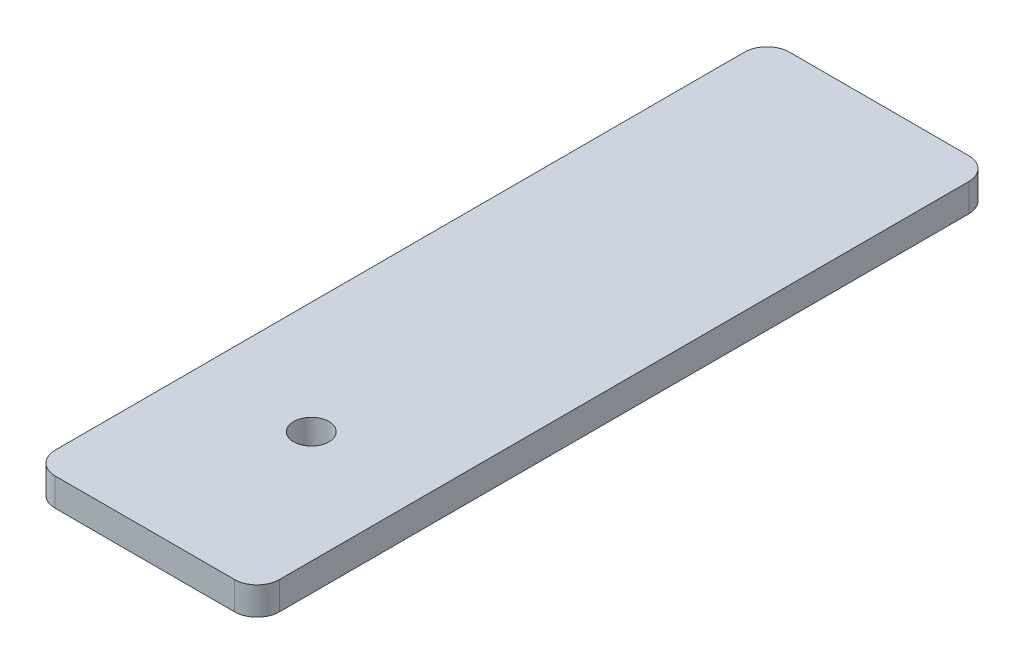
SolidWorks part; units mm, degrees
material "Acrylic (Medium-high impact)"
ref_plane "Front Plane" through (0, 0, 0) normal (0, 0, 1) x (1, 0, 0)
ref_plane "Top Plane" through (0, 0, 0) normal (0, 1, 0) x (1, 0, 0)
ref_plane "Right Plane" through (0, 0, 0) normal (1, 0, 0) x (0, 0, -1)
ref_plane "Plane1" through (0, 0, 0) normal (0, 1, 0) x (1, 0, 0)
sketch "Sketch1" plane through (0, 0, 0) normal (0, 1, 0) x (1, 0, 0)
  line L1 (-26.2811, -26.9588) -> (-0.8811, -26.9588)
  line L2 (-26.2811, -26.9588) -> (-26.2811, 56.2162)
  line L3 (-26.2811, 56.2162) -> (-0.8811, 56.2162)
  line L4 (-0.8811, -26.9588) -> (-0.8811, 56.2162)
  dimension "D1" = 83.175
  dimension "D2" = 25.4
extrude "Boss-Extrude1" add sketch "Sketch1" along normal blind 3.175
sketch "Sketch2" plane through (0, 3.175, 0) normal (0, 1, 0) x (1, 0, 0)
  line L0 (-26.2811, -26.9588) -> (-0.8811, -26.9588) construction
  line L1 (-26.2811, 56.2162) -> (-26.2811, -26.9588) construction
  circle A0 centre (-13.5811, -8.1088) radius 2
  dimension "D2" = 4
  dimension "D1" = 18.85
  dimension "D3" = 12.7
extrude "Cut-Extrude1" cut sketch "Sketch2" against normal through all
fillet "Fillet1" radius 2.54 4 edges at (-26.2811, 1.5875, -56.2162) (-0.8811, 1.5875, -56.2162) (-0.8811, 1.5875, 26.9588) (-26.2811, 1.5875, 26.9588)
